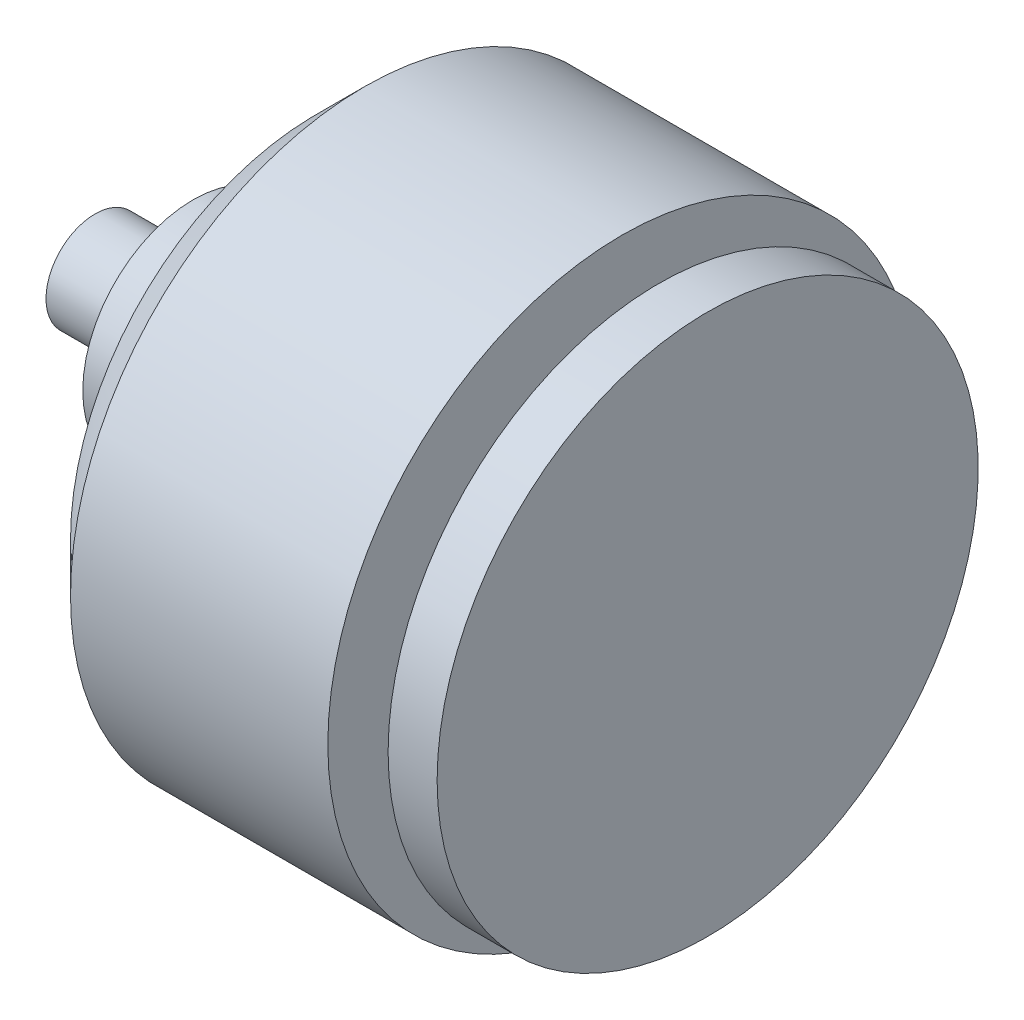
SolidWorks part; units mm, degrees
ref_plane "Front Plane" through (0, 0, 0) normal (0, 0, 1) x (1, 0, 0)
ref_plane "Top Plane" through (0, 0, 0) normal (0, 1, 0) x (1, 0, 0)
ref_plane "Right Plane" through (0, 0, 0) normal (1, 0, 0) x (0, 0, -1)
sketch "Sketch1" plane through (0, 0, 0) normal (0, 0, 1) x (1, 0, 0)
  line L0 (0, 0) -> (0, 22.08)
  line L1 (0, 22.08) -> (-4, 22.08)
  line L2 (-4, 22.08) -> (-4, 16.8)
  line L3 (-4, 16.8) -> (-7, 16.8)
  line L4 (-7, 16.8) -> (-7, 24)
  line L5 (-7, 24) -> (-28, 24)
  line L6 (-28, 24) -> (-32, 20)
  line L7 (-32, 20) -> (-32, 9)
  line L8 (-32, 9) -> (-42, 9)
  line L9 (-42, 9) -> (-42, 4)
  line L10 (-42, 4) -> (-50, 4)
  line L11 (-50, 4) -> (-50, 0)
  line L12 (-50, 0) -> (0, 0)
  line L13 (-10, 0) -> (1000, 0) construction
revolve "Revolve1" add sketch "Sketch1" angle 360 about L13
